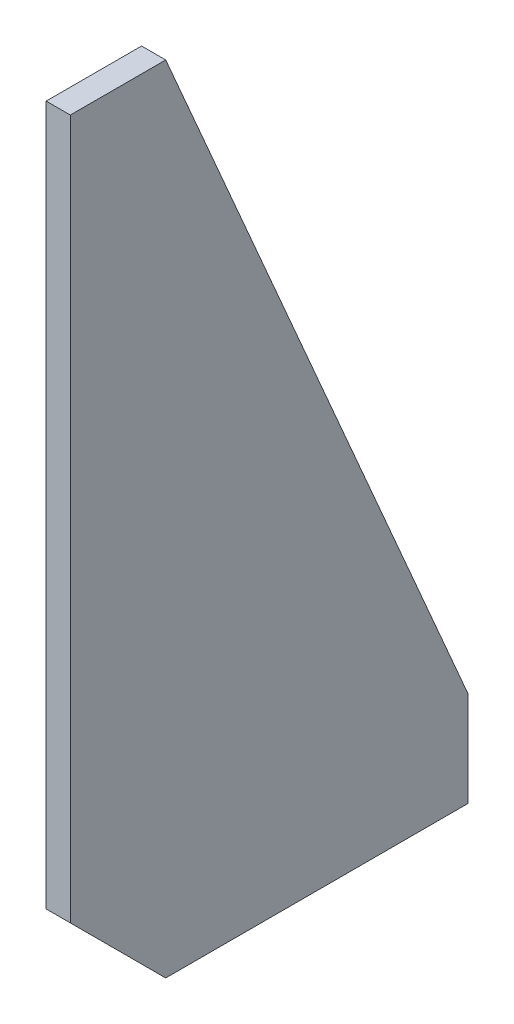
SolidWorks part; units mm, degrees
material "Low Carbon Steel"
ref_plane "Front Plane" through (0, 0, 0) normal (0, 0, 1) x (1, 0, 0)
ref_plane "Top Plane" through (0, 0, 0) normal (0, 1, 0) x (1, 0, 0)
ref_plane "Right Plane" through (0, 0, 0) normal (1, 0, 0) x (0, 0, -1)
sketch "Sketch1" plane through (0, 0, 0) normal (1, 0, 0) x (0, 0, -1)
  line L0 (12, 0) -> (0, 12)
  line L1 (0, 12) -> (0, 100)
  line L2 (0, 100) -> (12, 100)
  line L3 (12, 100) -> (50, 12)
  line L4 (50, 12) -> (50, 0)
  line L5 (50, 0) -> (12, 0)
  dimension "D1" = 50
  dimension "D2" = 100
  dimension "D3" = 12
  dimension "D4" = 12
  dimension "D5" = 12
  dimension "D6" = 12
base flange "Base-Flange1" sketch "Sketch1" thickness 3.0378 reverse thickness direction no parameters "D1"=3.175
other "Freeze***"
sketch "Bend-Lines1" plane through (0, 0, 0) normal (0, 1, 0) x (1, 0, 0)
sketch "Bounding-Box1" plane through (0, 0, 0) normal (0, 1, 0) x (1, 0, 0)
sheet metal parameters "Sheet-Metal16" thickness 3.0378 parameters "D1"=3.175
flat pattern "Flat-Pattern16" [suppressed]
sketch "Bend-Lines2" plane through (0, 0, 0) normal (0, 1, 0) x (1, 0, 0)
sketch "Bounding-Box2" [suppressed] plane through (0, 0, 0) normal (0, 1, 0) x (1, 0, 0)
